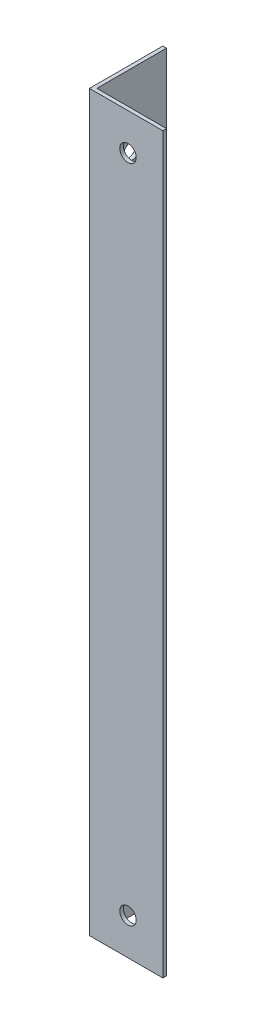
SolidWorks part; units mm, degrees
material "1060 Сплав"
ref_plane "Спереди" through (0, 0, 0) normal (0, 0, 1) x (1, 0, 0)
ref_plane "Сверху" through (0, 0, 0) normal (0, 1, 0) x (1, 0, 0)
ref_plane "Справа" through (0, 0, 0) normal (1, 0, 0) x (0, 0, -1)
sketch "Эскиз1" plane through (0, 0, 0) normal (0, 1, 0) x (1, 0, 0)
  line L0 (0, 0) -> (0, 20)
  line L1 (0, 20) -> (1, 20)
  line L2 (1, 20) -> (1, 1)
  line L3 (1, 1) -> (20, 1)
  line L4 (20, 1) -> (20, 0)
  line L5 (20, 0) -> (0, 0)
  dimension "D1" = 1
  dimension "D2" = 20
extrude "Бобышка-Вытянуть1" add sketch "Эскиз1" along normal blind 200
sketch "Эскиз2" plane through (1, 0, 0) normal (1, 0, 0) x (0, 0, -1)
  circle A0 centre (10.5, 29.5) radius 2.25 construction
  circle A1 centre (10.5, 29.5) radius 2.25
extrude "Вырез-Вытянуть1" cut sketch "Эскиз2" against normal through all
sketch "Эскиз3" plane through (0, 0, -1) normal (0, 0, -1) x (-1, 0, 0)
  line L0 (-10.5, 0) -> (-10.5, 10) construction
  line L1 (-20, 0) -> (-1, 0) construction
  circle A0 centre (-10.5, 10) radius 2.25
  dimension "D2" = 4.5
  dimension "D1" = 10
extrude "Вырез-Вытянуть2" cut sketch "Эскиз3" against normal through all
sketch "Эскиз4" plane through (0, 0, -1) normal (0, 0, -1) x (-1, 0, 0)
  line L0 (-10.5, 200) -> (-10.5, 190) construction
  line L1 (-20, 200) -> (-1, 200) construction
  circle A0 centre (-10.5, 190) radius 2.25
  dimension "D2" = 4.5
  dimension "D1" = 10
extrude "Вырез-Вытянуть3" cut sketch "Эскиз4" against normal through all
sketch "Эскиз5" plane through (1, 0, 0) normal (1, 0, 0) x (0, 0, -1)
  circle A0 centre (10.5, 180.5) radius 2.25 construction
  circle A1 centre (10.5, 180.5) radius 2.25
extrude "Вырез-Вытянуть4" cut sketch "Эскиз5" against normal through all
